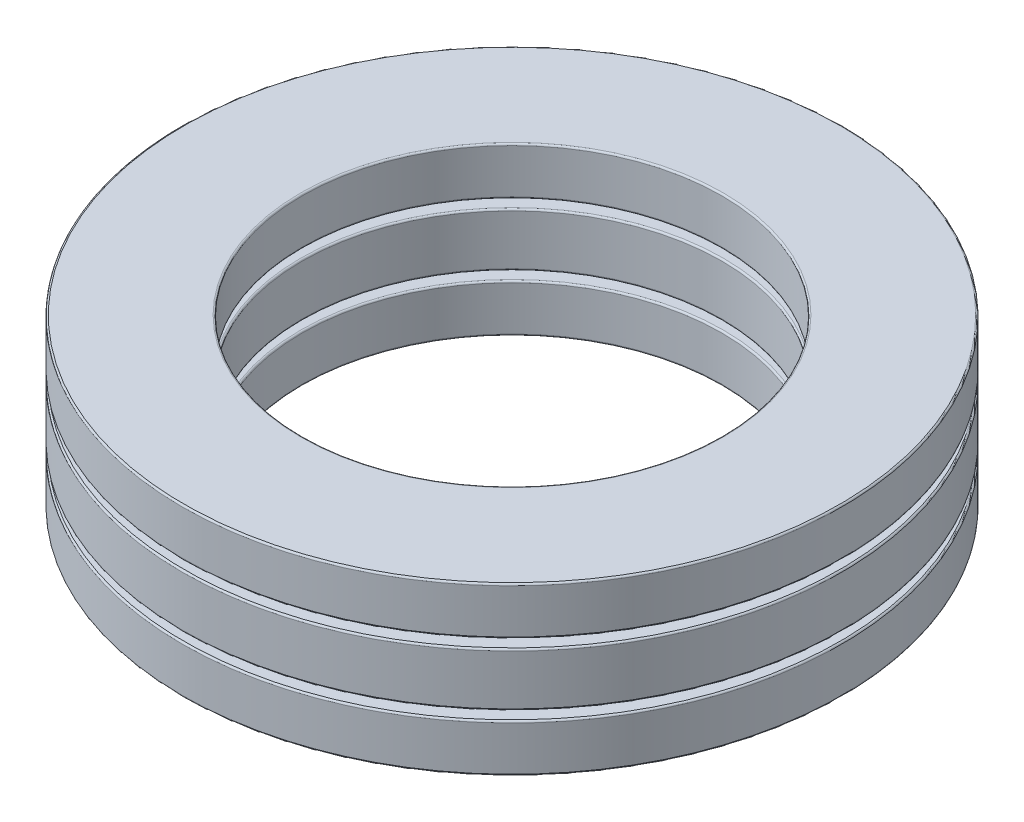
SolidWorks part; units mm, degrees
other "Imported8"
other "Imported2"
other "Imported1"
other "Imported3"
other "Imported4"
other "Imported5"
other "Imported6"
other "Imported9"
other "Imported7" parameters "Angle"=30, "Balls"=12, "D1"=12, "D2"=30, "OD"=28, "Shaft Dia"=8.0137, "Th"=8.74, "D3"=4.9022, "ID"=16.076, "E | Thickness"=4.92, "Thickness"=11.11, "Washer Thickness"=3.18, "F | Ball Diameter"=2, "Ball Diameter"=2
ref_plane "Front Plane" through (0, 0, 0) normal (0, 0, 1) x (1, 0, 0)
ref_plane "Top Plane" through (0, 0, 0) normal (0, 1, 0) x (1, 0, 0)
ref_plane "Right Plane" through (0, 0, 0) normal (1, 0, 0) x (0, 0, -1)
sketch "Sketch1" plane through (0, 0, 0) normal (0, 1, 0) x (1, 0, 0)
  circle A0 centre (0, 0) radius 22 construction
  circle A1 centre (0, 0) radius 14 construction
  circle A2 centre (0, 0) radius 18.25 construction
  dimension "OD" = 44
  dimension "Ball Circle" = 36.5
  dimension "ID" = 28
sketch "Sketch2" plane through (0, 0, 0) normal (0, 0, -1) x (-1, 0, 0)
  line L0 (-22, 5.555) -> (-22, 2.375) construction
  line L1 (-22, 0) -> (0, 0) construction
  line L3 (0, 5.555) -> (0, -5.555) construction
  line L4 (-22, 2.375) -> (-22, -2.375) construction
  line L6 (-22, -2.375) -> (-22, -5.555) construction
  point P11 (-22, 0)
sketch "Sketch3" plane through (0, 0, 0) normal (0, 0, 1) x (1, 0, 0)
  line L2 (22, 1.7813) -> (14, 1.7812)
  line L4 (22, 1.7813) -> (22, -1.7812)
  line L7 (22, -1.7812) -> (14, -1.7812)
  line L8 (14, 1.7812) -> (14, -1.7812)
  line L11 (22, 2.375) -> (22, -2.375) construction
  point P8 (14, 0)
  dimension "D1" = 3.5625
revolve "Revolve1" add sketch "Sketch3" angle 360 about L3
sketch "Sketch4" plane through (0, 0, 0) normal (0, 0, 1) x (1, 0, 0)
  line L0 (18.25, 2.375) -> (18.25, -2.375)
  arc A0 (18.25, 2.375) -> (18.25, -2.375) centre (18.25, 0) ccw
revolve "Cut-Revolve1" cut sketch "Sketch4" angle 360 about L0
sketch "Sketch5" plane through (0, 0, 0) normal (0, 0, 1) x (1, 0, 0)
  line L0 (18.25, 2.375) -> (18.25, -2.375)
  arc A0 (18.25, 2.375) -> (18.25, -2.375) centre (18.25, 0) ccw
revolve "Revolve2" add sketch "Sketch5" angle 360 about L0
pattern_circular "CirPattern1" count 12 every 30 about axis through (0, 5.555, 0) along (0, -1, 0) of bodies 187
pattern_circular "CirPattern2" count 12 every 30 about axis through (0, 0, 0) along (0, 1, 0) of "Cut-Revolve1"
sketch "Sketch6" plane through (0, 0, 0) normal (0, 0, 1) x (1, 0, 0)
  line L2 (22, 5.555) -> (14, 5.555)
  line L3 (22, 5.555) -> (22, 2.375)
  line L4 (22, 2.375) -> (14, 2.375)
  line L5 (14, 5.555) -> (14, 2.375)
  line L6 (22, -2.375) -> (14, -2.375)
  line L7 (22, -2.375) -> (22, -5.555)
  line L8 (22, -5.555) -> (14, -5.555)
  line L13 (14, -2.375) -> (14, -5.555)
  point P11 (14, 0)
revolve "Revolve3" add sketch "Sketch6" angle 360 about L3
fillet "Fillet1" radius 0.1111 4 edges at (0, 2.375, 14) (0, 2.375, 22) (0, 5.555, 22) (0, 5.555, 14)
fillet "Fillet2" radius 0.1111 28 edges at (0, -1.7812, 14) (0, -1.7812, 22) (18.25, -1.7812, 1.5709) (15.0195, -1.7812, 10.4855) (7.7645, -1.7812, 16.5904) (-1.5709, -1.7812, 18.25) (-10.4855, -1.7812, 15.0195) (-16.5904, -1.7812, 7.7645) (-18.25, -1.7812, -1.5709) (0, 1.7813, 22) (0, 1.7812, 14) (18.25, 1.7813, -1.5709) (16.5904, 1.7813, 7.7645) (10.4855, 1.7813, 15.0195) (1.5709, 1.7813, 18.25) (-7.7645, 1.7813, 16.5904) (-15.0195, 1.7813, 10.4855) (-18.25, 1.7813, 1.5709) (-15.0195, -1.7812, -10.4855) (-16.5904, 1.7813, -7.7645) (-7.7645, -1.7812, -16.5904) (1.5709, -1.7812, -18.25) (10.4855, -1.7812, -15.0195) (16.5904, -1.7812, -7.7645) (-10.4855, 1.7813, -15.0195) (-1.5709, 1.7813, -18.25) (7.7645, 1.7813, -16.5904) (15.0195, 1.7813, -10.4855)
fillet "Fillet3" radius 0.1111 4 edges at (0, -2.375, 22) (0, -2.375, 14) (0, -5.555, 14) (0, -5.555, 22)
equation "\"Angle@CirPattern1\" = 360/\"Balls@CirPattern1\""
equation "\"D1@CirPattern2\" = \"Balls@CirPattern1\""
equation "\"D2@CirPattern2\" = \"Angle@CirPattern1\""
equation "\"D1@Sketch3\" =  ( \"Thickness@Sketch2\" -  ( 2 * \"Washer Thickness@Sketch2\" )  )  * .75"
equation "\"D1@Fillet1\" = \"Thickness@Sketch2\" * .01"
equation "\"D1@Fillet2\"=\"D1@Fillet1\""
equation "\"D1@Fillet3\"=\"D1@Fillet1\""
